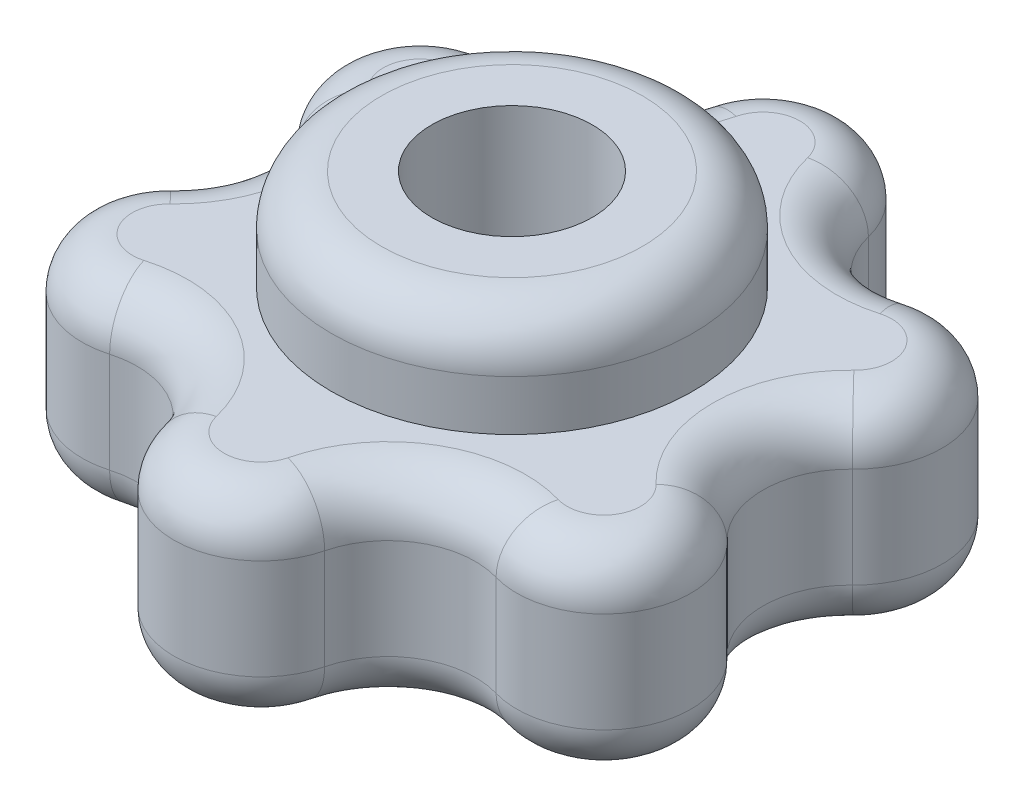
SolidWorks part; units mm, degrees
ref_plane "Спереди" through (0, 0, 0) normal (0, 0, 1) x (1, 0, 0)
ref_plane "Сверху" through (0, 0, 0) normal (0, 1, 0) x (1, 0, 0)
ref_plane "Справа" through (0, 0, 0) normal (1, 0, 0) x (0, 0, -1)
sketch "Эскиз1" plane through (0, 0, 0) normal (0, 1, 0) x (1, 0, 0)
  line L1 (0, 3.3486) -> (-2.9, 1.6743)
  line L2 (-2.9, 1.6743) -> (-2.9, -1.6743)
  line L3 (-2.9, -1.6743) -> (0, -3.3486)
  line L4 (0, -3.3486) -> (2.9, -1.6743)
  line L5 (2.9, -1.6743) -> (2.9, 1.6743)
  line L6 (2.9, 1.6743) -> (0, 3.3486)
  circle A0 centre (0, 0) radius 5 construction
  arc A1 (1.6835, 5.416) -> (-1.6835, 5.416) centre (0, 5) ccw
  arc A2 (1.6835, 5.416) -> (3.8486, 4.166) centre (3.3671, 5.832) ccw
  arc A3 (-1.6835, -5.416) -> (1.6835, -5.416) centre (0, -5) ccw
  arc A4 (3.8486, -4.166) -> (1.6835, -5.416) centre (3.3671, -5.832) ccw
  arc A5 (5.5322, 1.25) -> (3.8486, 4.166) centre (4.3301, 2.5) ccw
  arc A6 (5.5322, 1.25) -> (5.5322, -1.25) centre (6.7342, 0) ccw
  arc A7 (3.8486, -4.166) -> (5.5322, -1.25) centre (4.3301, -2.5) ccw
  arc A8 (-3.8486, 4.166) -> (-1.6835, 5.416) centre (-3.3671, 5.832) ccw
  arc A9 (-3.8486, 4.166) -> (-5.5322, 1.25) centre (-4.3301, 2.5) ccw
  arc A10 (-5.5322, -1.25) -> (-5.5322, 1.25) centre (-6.7342, 0) ccw
  arc A11 (-1.6835, -5.416) -> (-3.8486, -4.166) centre (-3.3671, -5.832) ccw
  arc A12 (-5.5322, -1.25) -> (-3.8486, -4.166) centre (-4.3301, -2.5) ccw
  circle A13 centre (0, 0) radius 2.9 construction
  dimension "D1" = 10
extrude "Бобышка-Вытянуть1" add sketch "Эскиз1" along normal blind 4 contours A7 A6 A5 A2 A1 A8 A9 A10 A12 A11 A3 A4
sketch "Эскиз2" plane through (0, 4, 0) normal (0, 1, 0) x (1, 0, 0)
  circle A0 centre (0, 0) radius 3.6
  dimension "D1" = 7.2
extrude "Бобышка-Вытянуть2" add sketch "Эскиз2" along normal blind 2
sketch "Эскиз3" plane through (0, 6, 0) normal (0, 1, 0) x (1, 0, 0)
  circle A0 centre (0, 0) radius 1.6
  dimension "D1" = 3.2
extrude "Вырез-Вытянуть1" cut sketch "Эскиз3" against normal through all
extrude "Вырез-Вытянуть2" cut sketch "Эскиз1<3>" along normal blind 2.5 contours L1 L2 L3 L4 L5 L6
sketch "Эскиз1<3>" plane through (0, 0, 0) normal (0, 1, 0) x (1, 0, 0) same geometry as "Эскиз1"
fillet "Скругление1" radius 1 25 edges at (-2.5, 4, 4.3301) (-5.832, 4, 3.3671) (-5, 4, 0) (-5.832, 4, -3.3671) (-2.5, 4, -4.3301) (0, 4, -6.7342) (2.5, 4, -4.3301) (5.832, 4, -3.3671) (5, 4, 0) (5.832, 4, 3.3671) (2.5, 4, 4.3301) (-2.5, 0, 4.3301) (-5.832, 0, 3.3671) (-5, 0, 0) (-5.832, 0, -3.3671) (-2.5, 0, -4.3301) (0, 0, -6.7342) (2.5, 0, -4.3301) (5.832, 0, -3.3671) (5, 0, 0) (5.832, 0, 3.3671) (2.5, 0, 4.3301) (0, 6, 3.6) (0, 4, 6.7342) (0, 0, 6.7342)
